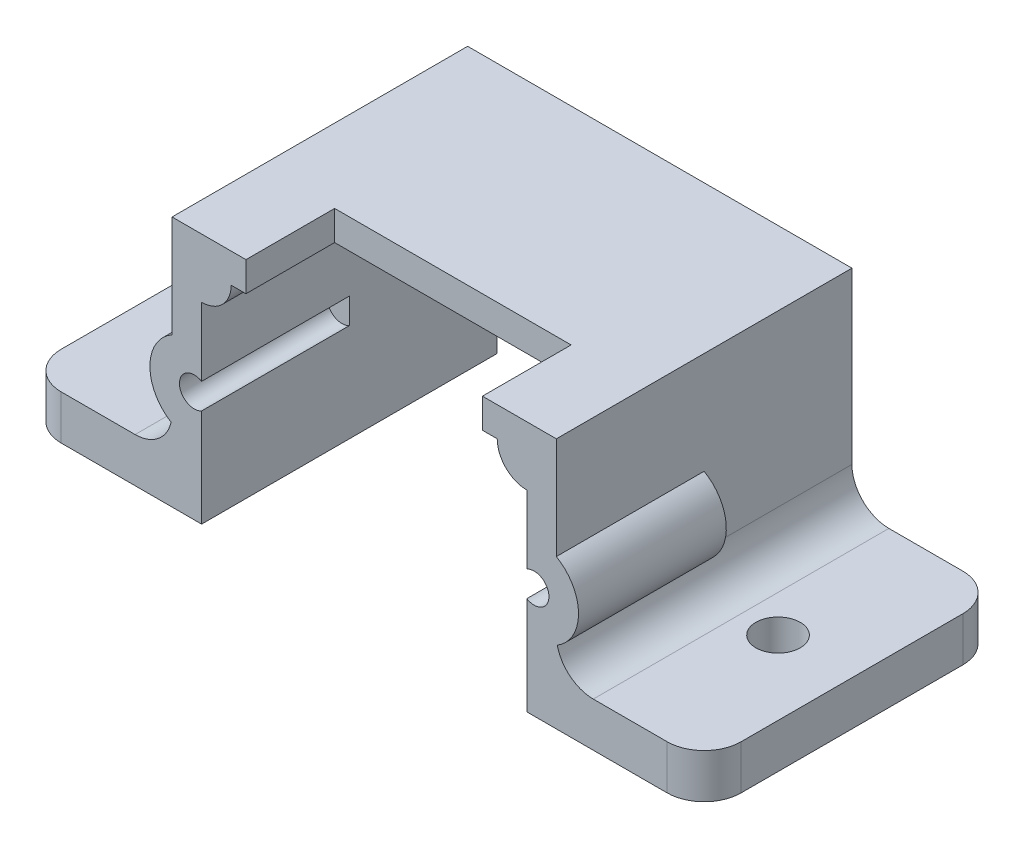
SolidWorks part; units mm, degrees
ref_plane "前视基准面" through (0, 0, 0) normal (0, 0, 1) x (1, 0, 0)
ref_plane "上视基准面" through (0, 0, 0) normal (0, 1, 0) x (1, 0, 0)
ref_plane "右视基准面" through (0, 0, 0) normal (1, 0, 0) x (0, 0, -1)
sketch "草图1" plane through (0, 0, 0) normal (0, 0, 1) x (1, 0, 0)
  line L0 (-15.0735, 6.6657) -> (10.9265, 6.6657)
  line L1 (-13.0735, 4.6657) -> (8.9265, 4.6657)
  line L2 (-13.0735, 4.6657) -> (-13.0735, -1.9683)
  line L4 (8.9265, 4.6657) -> (8.9265, -1.9683)
  line L5 (10.9265, 6.6657) -> (10.9265, -0.2362)
  line L6 (-13.0735, -3.7003) -> (-13.0735, -10.3343)
  line L7 (8.9265, -3.7003) -> (8.9265, -10.3343)
  line L8 (10.9265, -5.4324) -> (10.9265, -10.3343)
  line L10 (-15.0735, -5.4324) -> (-15.0735, -10.3343)
  line L11 (-15.0735, 6.6657) -> (-15.0735, -0.2362)
  line L12 (-13.0735, -10.3343) -> (-15.0735, -10.3343)
  line L13 (8.9265, -10.3343) -> (10.9265, -10.3343)
  line L15 (-15.0735, -5.4324) -> (-15.0735, -12.3343) construction
  line L16 (-13.0735, -10.3343) -> (8.9265, -10.3343) construction
  line L17 (-15.0735, -12.3343) -> (10.9265, -12.3343) construction
  line L18 (10.9265, -5.4324) -> (10.9265, -12.3343) construction
  arc A0 (8.9265, -3.7003) -> (8.9265, -1.9683) centre (9.4265, -2.8343) ccw
  arc A1 (-13.0735, -1.9683) -> (-13.0735, -3.7003) centre (-13.5735, -2.8343) ccw
  arc A2 (10.9265, -5.4324) -> (10.9265, -0.2362) centre (9.4265, -2.8343) ccw
  arc A3 (-15.0735, -0.2362) -> (-15.0735, -5.4324) centre (-13.5735, -2.8343) ccw
  dimension "D1" = 2
extrude "凸台-拉伸1" add sketch "草图1" along normal blind 20
sketch "草图2" plane through (0, 6.6657, 0) normal (0, 1, 0) x (1, 0, 0)
  line L1 (10.9265, -20) -> (-15.0735, -20) construction
  line L2 (-2.0735, -14) -> (-10.0735, -14)
  line L3 (-2.0735, -14) -> (5.9265, -14)
  line L4 (5.9265, -14) -> (5.9265, -20)
  line L5 (5.9265, -20) -> (-10.0735, -20)
  line L6 (-10.0735, -20) -> (-10.0735, -14)
extrude "切除-拉伸1" cut sketch "草图2" against normal blind 20
sketch "草图3" plane through (0, 0, 20) normal (0, 0, 1) x (1, 0, 0)
  line L0 (-13.0735, 4.6657) -> (-13.0735, 2.6657)
  line L1 (-13.0735, 4.6657) -> (-11.0735, 4.6657)
  line L2 (8.9265, 4.6657) -> (8.9265, 2.6657)
  line L3 (8.9265, 4.6657) -> (6.9265, 4.6657)
  arc A0 (-13.0735, 2.6657) -> (-11.0735, 4.6657) centre (-13.0735, 4.6657) ccw
  arc A1 (6.9265, 4.6657) -> (8.9265, 2.6657) centre (8.9265, 4.6657) ccw
extrude "凸台-拉伸2" add sketch "草图3" against normal blind 12.5
sketch "草图4" plane through (0, 0, 0) normal (0, 0, -1) x (-1, 0, 0)
  line L1 (-10.9265, -0.2362) -> (-15.1348, -0.2362)
  line L2 (-10.9265, -0.2362) -> (-10.9265, -6.0887)
  line L3 (-10.9265, -6.0887) -> (-15.1348, -6.0887)
  line L4 (-15.1348, -0.2362) -> (-15.1348, -6.0887)
  line L5 (15.0735, -0.2362) -> (21.8834, -0.2362)
  line L6 (15.0735, -0.2362) -> (15.0735, -5.8399)
  line L7 (15.0735, -5.8399) -> (21.8834, -5.8399)
  line L8 (21.8834, -0.2362) -> (21.8834, -5.8399)
extrude "切除-拉伸2" cut sketch "草图4" against normal blind 10
sketch "草图5" plane through (0, 0, 0) normal (0, 0, -1) x (-1, 0, 0)
  line L0 (-8.9265, -1.9683) -> (-8.9265, -3.7003)
  line L1 (13.0735, -1.9683) -> (13.0735, -3.7003)
  line L10 (-10.9265, 6.6657) -> (-10.9265, -10.3343)
  line L11 (-10.9265, -10.3343) -> (-8.9265, -10.3343)
  line L12 (-8.9265, -10.3343) -> (-8.9265, -3.7003)
  line L13 (-8.9265, -1.9683) -> (-8.9265, 4.6657)
  line L14 (-8.9265, 4.6657) -> (13.0735, 4.6657)
  line L15 (13.0735, 4.6657) -> (13.0735, -1.9683)
  line L16 (13.0735, -3.7003) -> (13.0735, -10.3343)
  line L17 (13.0735, -10.3343) -> (15.0735, -10.3343)
  line L18 (15.0735, -10.3343) -> (15.0735, 6.6657)
  line L19 (15.0735, 6.6657) -> (-10.9265, 6.6657)
  arc A2 (-8.9265, -1.9683) -> (-8.9265, -3.7003) centre (-9.4265, -2.8343) ccw
  arc A3 (13.0735, -3.7003) -> (13.0735, -1.9683) centre (13.5735, -2.8343) ccw
  arc A4 (-8.9265, -1.9683) -> (-8.9265, -3.7003) centre (-9.4265, -2.8343) ccw
  arc A5 (13.0735, -3.7003) -> (13.0735, -1.9683) centre (13.5735, -2.8343) ccw
  dimension "D1" = 0
extrude "凸台-拉伸3" add sketch "草图5" against normal blind 10
sketch "草图6" plane through (0, -10.3343, 0) normal (0, -1, 0) x (1, 0, 0)
  line L1 (10.9265, 0) -> (20.9265, 0)
  line L2 (10.9265, 0) -> (10.9265, 20)
  line L3 (10.9265, 20) -> (20.9265, 20)
  line L4 (20.9265, 0) -> (20.9265, 20)
  line L5 (-15.0735, 0) -> (-25.0735, 0)
  line L6 (-15.0735, 0) -> (-15.0735, 20)
  line L7 (-15.0735, 20) -> (-25.0735, 20)
  line L8 (-25.0735, 0) -> (-25.0735, 20)
extrude "凸台-拉伸4" add sketch "草图6" against normal blind 3
sketch "草图7" plane through (0, -7.3343, 0) normal (0, 1, 0) x (1, 0, 0)
  circle A0 centre (15.9265, -10) radius 1.5
  circle A1 centre (-20.0735, -10) radius 1.5
extrude "切除-拉伸3" cut sketch "草图7" against normal blind 3
fillet "圆角1" radius 2.5 6 edges at (-15.0735, -7.3343, 10) (10.9265, -7.3343, 10) (20.9265, -8.8343, 20) (-25.0735, -8.8343, 20) (20.9265, -8.8343, 0) (-25.0735, -8.8343, 0)
